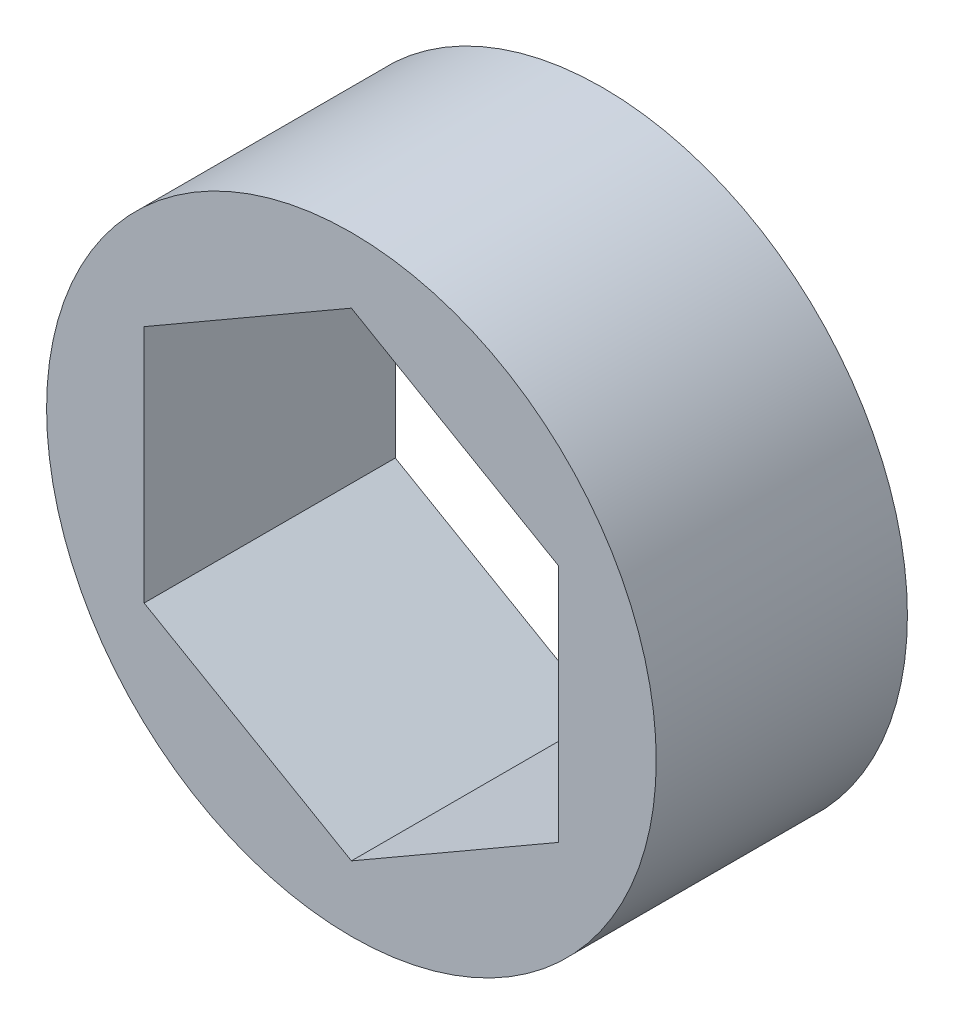
SolidWorks part; units mm, degrees
material "PET"
ref_plane "Front Plane" through (0, 0, 0) normal (0, 0, 1) x (1, 0, 0)
ref_plane "Top Plane" through (0, 0, 0) normal (0, 1, 0) x (1, 0, 0)
ref_plane "Right Plane" through (0, 0, 0) normal (1, 0, 0) x (0, 0, -1)
sketch "Sketch1" plane through (0, 0, 0) normal (0, 0, 1) x (1, 0, 0)
  line L1 (0, 7.479) -> (-6.477, 3.7395)
  line L2 (-6.477, 3.7395) -> (-6.477, -3.7395)
  line L3 (-6.477, -3.7395) -> (0, -7.479)
  line L4 (0, -7.479) -> (6.477, -3.7395)
  line L5 (6.477, -3.7395) -> (6.477, 3.7395)
  line L6 (6.477, 3.7395) -> (0, 7.479)
  circle A0 centre (0, 0) radius 9.525
  circle A1 centre (0, 0) radius 6.477 construction
  dimension "D1" = 12.954
  dimension "D2" = 19.05
extrude "Boss-Extrude1" add sketch "Sketch1" along normal mid plane 7.8486
